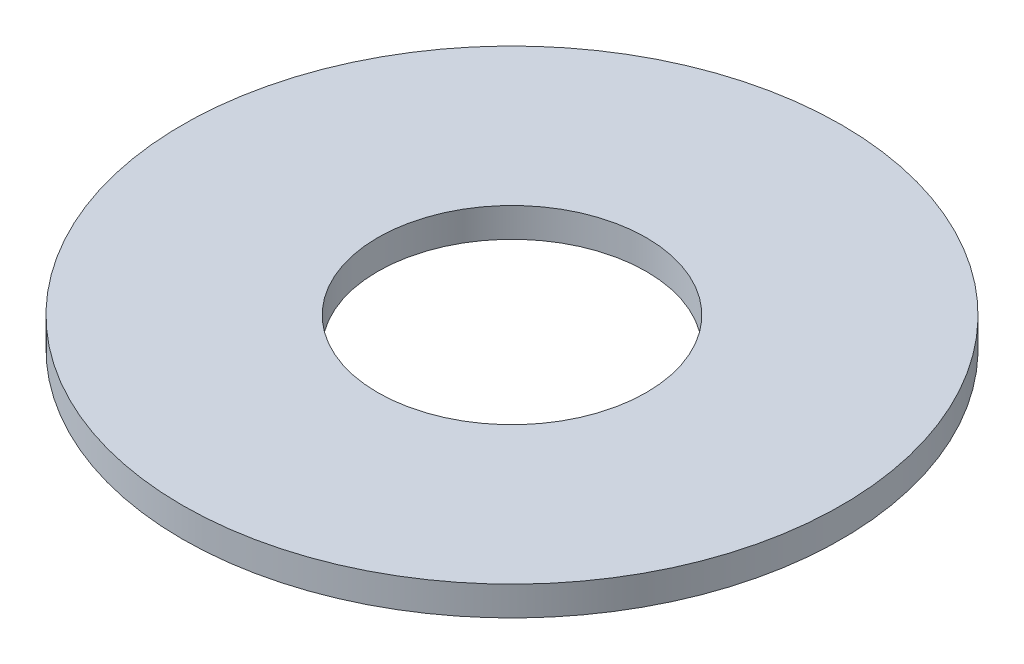
SolidWorks part; units mm, degrees
ref_plane "Front Plane" through (0, 0, 0) normal (0, 0, 1) x (1, 0, 0)
ref_plane "Top Plane" through (0, 0, 0) normal (0, 1, 0) x (1, 0, 0)
ref_plane "Right Plane" through (0, 0, 0) normal (1, 0, 0) x (0, 0, -1)
sketch "Sketch1" plane through (0, 0, 0) normal (0, 1, 0) x (1, 0, 0)
  circle A0 centre (0, 0) radius 67.5
  dimension "FLANGE_OD" = 135
extrude "Boss-Extrude1" add sketch "Sketch1" along normal blind 6
sketch "Sketch2" plane through (0, 0, 0) normal (0, 1, 0) x (1, 0, 0)
  circle A0 centre (0, 0) radius 27.5
  dimension "BORE_D" = 55
extrude "Cut-Extrude1" cut sketch "Sketch2" along normal through all
sketch "Sketch3" plane through (0, 6, 0) normal (0, 1, 0) x (1, 0, 0)
  circle A0 centre (0, 0) radius 16.9699 construction
  circle A1 centre (-16.9699, 0) radius 3.3669
  dimension "BOLT_D" = 6.7338
  dimension "BOLT_PCD" = 33.9397
extrude "Cut-Extrude2" cut sketch "Sketch3" against normal blind 3.684 rebuild error yes
pattern_circular "CirPattern1" count 3 over 360 rebuild error yes
